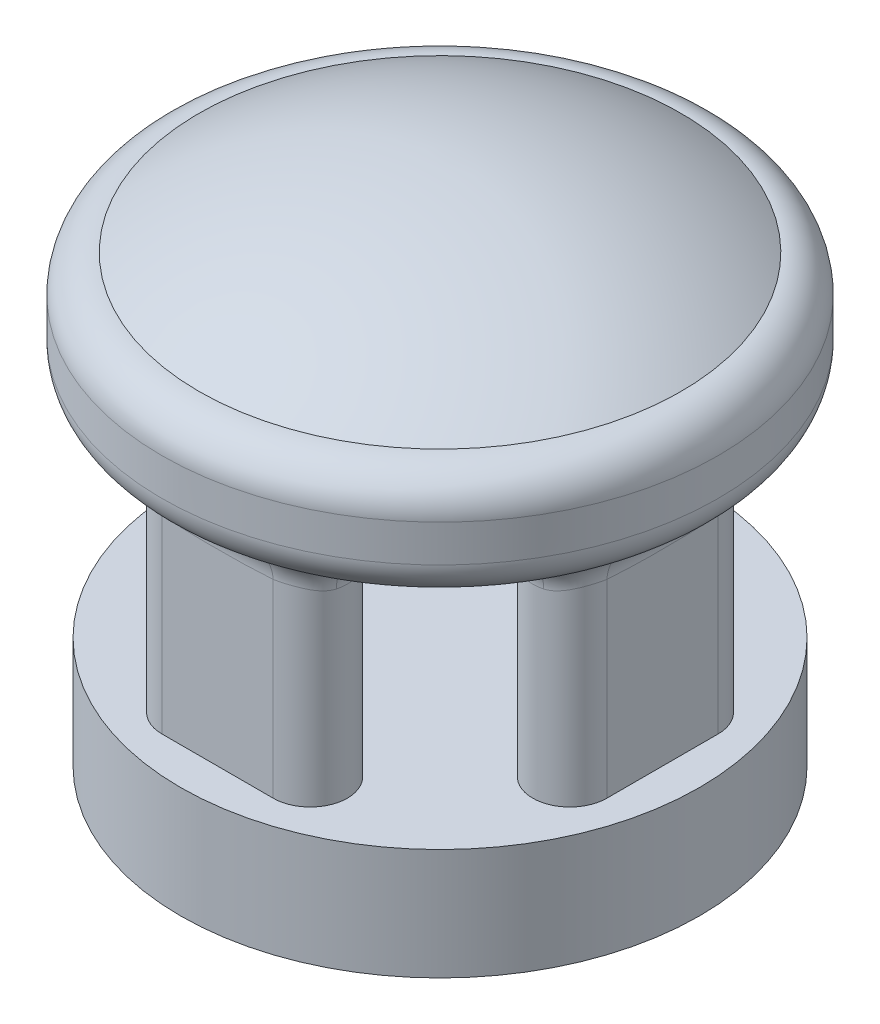
SolidWorks part; units mm, degrees
ref_plane "Front Plane" through (0, 0, 0) normal (0, 0, 1) x (1, 0, 0)
ref_plane "Top Plane" through (0, 0, 0) normal (0, 1, 0) x (1, 0, 0)
ref_plane "Right Plane" through (0, 0, 0) normal (1, 0, 0) x (0, 0, -1)
sketch "Sketch1" plane through (0, 0, 0) normal (0, 1, 0) x (1, 0, 0)
  circle A0 centre (0, 0) radius 9.525
  dimension "D1" = 19.05
extrude "button top" add sketch "Sketch1" along normal blind 3.81
sketch "Sketch2" plane through (0, 0, 0) normal (0, -1, 0) x (1, 0, 0)
  line L9 (-1.905, 6.35) -> (1.905, 6.35) construction
  line L10 (-1.905, 7.62) -> (1.905, 7.62)
  line L11 (-1.905, 5.08) -> (1.905, 5.08)
  arc A6 (-1.905, 7.62) -> (-1.905, 5.08) centre (-1.905, 6.35) ccw
  arc A7 (1.905, 5.08) -> (1.905, 7.62) centre (1.905, 6.35) ccw
  point P22 (0, 6.35)
  dimension "D2" = 1.27
  dimension "D1" = 6.35
  dimension "D8" = 3.81
extrude "connecting leg" add sketch "Sketch2" along normal blind 7.62
ref_axis "central axis" through (0, 3.81, 0) along (0, -1, 0)
pattern_circular "moar legs" count 4 over 360 about axis through (0, 3.81, 0) along (0, -1, 0) of "connecting leg"
ref_plane "base plane" through (0, -7.62, 0) normal (0, -1, 0) x (-1, 0, 0)
sketch "Sketch3" plane through (0, -7.62, 0) normal (0, -1, 0) x (-1, 0, 0)
  circle A0 centre (0, 0) radius 8.89
extrude "base" add sketch "Sketch3" along normal blind 3.81 separate body
fillet "round top" radius 1.27 2 edges at (0, 3.81, 9.525) (0, 0, 9.525)
fillet "round bars" radius 1.27 16 edges at (0, 0, 5.08) (-3.175, 0, 6.35) (0, 0, 7.62) (3.175, 0, 6.35) (5.08, 0, 0) (6.35, 0, 3.175) (7.62, 0, 0) (6.35, 0, -3.175) (3.175, 0, -6.35) (0, 0, -7.62) (-3.175, 0, -6.35) (0, 0, -5.08) (-5.08, 0, 0) (-6.35, 0, -3.175) (-7.62, 0, 0) (-6.35, 0, 3.175)
dome "button ness" faces to dome 1 distance 2.54 reverse direction no elliptical dome no face at (0, 3.81, 8.255) parameters "D1"=2.54
ref_point "center of face"
sketch "Sketch6" plane through (0, -11.43, 0) normal (0, -1, 0) x (1, 0, 0)
  circle A0 centre (0, 0) radius 2.54
extrude "flag" add sketch "Sketch6" along normal blind 0.254
fillet "flag fillet" radius 2.54 1 edges at (0, -11.43, -2.54)
